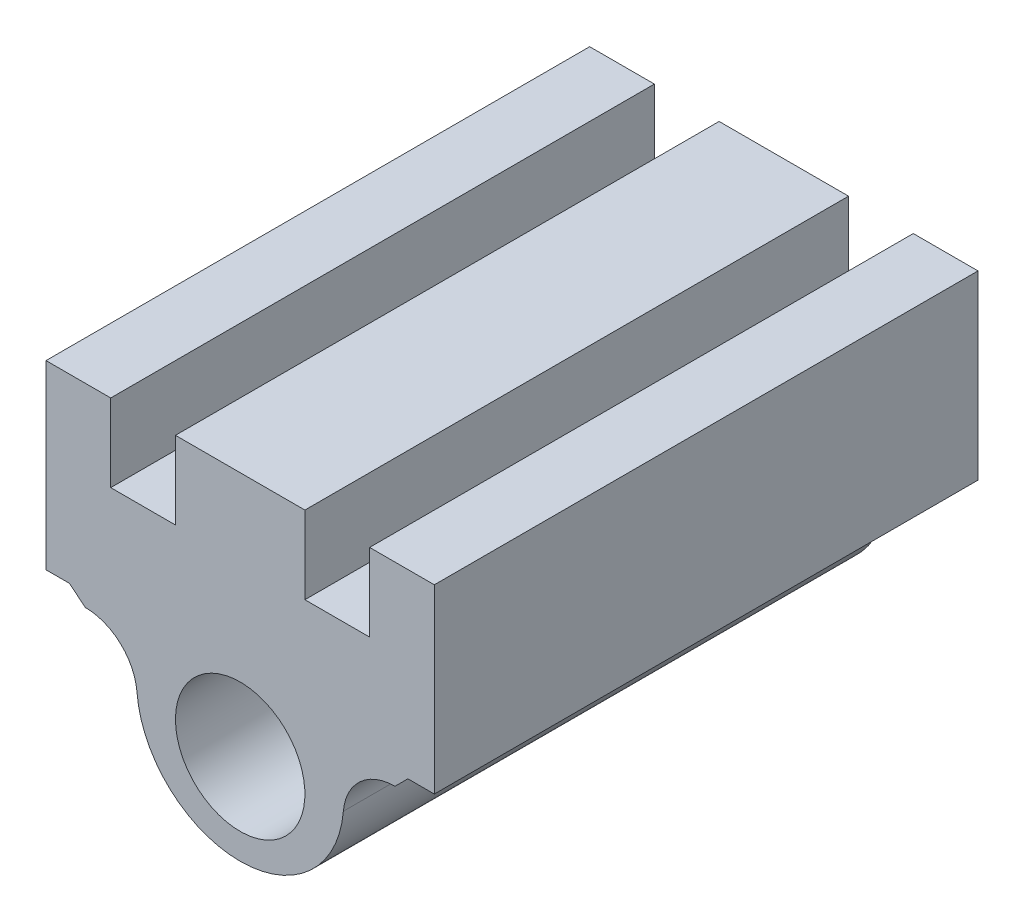
SolidWorks part; units mm, degrees
ref_plane "Front Plane" through (0, 0, 0) normal (0, 0, 1) x (1, 0, 0)
ref_plane "Top Plane" through (0, 0, 0) normal (0, 1, 0) x (1, 0, 0)
ref_plane "Right Plane" through (0, 0, 0) normal (1, 0, 0) x (0, 0, -1)
sketch "Sketch1" plane through (0, 0, 0) normal (0, 1, 0) x (1, 0, 0)
  line L1 (0, 0) -> (60, 0)
  line L2 (0, 0) -> (0, 42)
  line L3 (0, 42) -> (60, 42)
  line L4 (60, 0) -> (60, 42)
  dimension "D1" = 42
  dimension "D2" = 60
extrude "Boss-Extrude1" add sketch "Sketch1" along normal blind 8
sketch "Sketch3" plane through (0, 8, 0) normal (0, 1, 0) x (1, 0, 0)
  line L0 (60, 42) -> (0, 42) construction
  line L1 (25, 42) -> (35, 42)
  line L2 (25, 42) -> (25, 0)
  line L3 (25, 0) -> (35, 0)
  line L4 (35, 42) -> (35, 0)
  line L5 (0, 0) -> (60, 0) construction
  line L6 (0, 42) -> (0, 0) construction
  dimension "D1" = 10
  dimension "D2" = 25
extrude "Boss-Extrude5" add sketch "Sketch3" along normal blind 6
sketch "Sketch5" plane through (0, 0, 0) normal (0, -1, 0) x (1, 0, 0)
  line L0 (0, 0) -> (60, 0) construction
  line L1 (23, 0) -> (37, 0)
  line L2 (23, 0) -> (23, -42)
  line L3 (23, -42) -> (37, -42)
  line L4 (37, 0) -> (37, -42)
  line L5 (60, -42) -> (0, -42) construction
  line L6 (0, -42) -> (0, 0) construction
  dimension "D1" = 14
  dimension "D2" = 23
extrude "Boss-Extrude6" add sketch "Sketch5" along normal blind 11
sketch "Sketch6" plane through (0, 0, -42) normal (0, 0, -1) x (-1, 0, 0)
  line L0 (-23, -11) -> (-23, 0) construction
  line L1 (-37, -11) -> (-37, 0) construction
  line L2 (-23, -11) -> (-37, -11) construction
  circle A0 centre (-30, -5) radius 5
  dimension "D1" = 7
  dimension "D2" = 14
  dimension "D3" = 6
extrude "Cut-Extrude1" cut sketch "Sketch6" against normal through all
fillet "Fillet1" radius 7 2 edges at (23, -11, -21) (37, -11, -21)
fillet "Fillet2" radius 5 1 edges at (23, 0, -21)
fillet "Fillet3" radius 5 1 edges at (37, 0, -21)
sketch "Sketch8" plane through (0, 0, -42) normal (0, 0, -1) x (-1, 0, 0)
  line L0 (-41.9583, -1) -> (-42.9583, 0)
  line L1 (-60, 0) -> (-41.9583, 0) construction
  line L2 (-42.9583, 0) -> (-41.9583, 0)
  line L3 (-18.0417, -1) -> (-16.803, 0)
  line L4 (-18.0417, 0) -> (0, 0) construction
  line L5 (-16.803, 0) -> (-18.0417, 0)
  arc A0 (-18.0417, 0) -> (-23.0243, -4.5833) centre (-18.0417, -5) ccw construction
  arc A1 (-30, -11) -> (-23.0243, -4.5833) centre (-30, -4) ccw construction
  arc A2 (-36.9757, -4.5833) -> (-30, -11) centre (-30, -4) ccw construction
  arc A3 (-36.9757, -4.5833) -> (-41.9583, 0) centre (-41.9583, -5) ccw construction
  arc A4 (-18.0417, 0) -> (-23.0243, -4.5833) centre (-18.0417, -5) ccw
  arc A5 (-30, -11) -> (-23.0243, -4.5833) centre (-30, -4) ccw
  arc A6 (-36.9757, -4.5833) -> (-30, -11) centre (-30, -4) ccw
  arc A7 (-36.9757, -4.5833) -> (-41.9583, 0) centre (-41.9583, -5) ccw
  arc A8 (-18.0417, -1) -> (-22.0278, -4.6667) centre (-18.0417, -5) ccw
  arc A9 (-30, -12) -> (-22.0278, -4.6667) centre (-30, -4) ccw
  arc A10 (-37.9722, -4.6667) -> (-30, -12) centre (-30, -4) ccw
  arc A11 (-37.9722, -4.6667) -> (-41.9583, -1) centre (-41.9583, -5) ccw
  dimension "D1" = 1
extrude "Boss-Extrude7" add sketch "Sketch8" against normal up to surface (42 mm away) up to face at (25, -5, 0)
sketch "Sketch9" plane through (0, 8, 0) normal (0, 1, 0) x (1, 0, 0)
  line L0 (60, 42) -> (35, 42) construction
  line L1 (40, 42) -> (45, 42)
  line L2 (40, 42) -> (40, 0)
  line L3 (40, 0) -> (45, 0)
  line L4 (45, 42) -> (45, 0)
  line L5 (35, 0) -> (60, 0) construction
  line L6 (35, 0) -> (35, 42) construction
  line L7 (25, 42) -> (0, 42) construction
  line L8 (15, 42) -> (20, 42)
  line L9 (15, 42) -> (15, 0)
  line L10 (15, 0) -> (20, 0)
  line L11 (20, 42) -> (20, 0)
  line L12 (0, 0) -> (25, 0) construction
  line L13 (25, 42) -> (25, 0) construction
  dimension "D1" = 5
  dimension "D2" = 5
  dimension "D3" = 5
  dimension "D4" = 5
extrude "Boss-Extrude8" add sketch "Sketch9" along normal blind 6
sketch "Sketch11" plane through (0, 8, 0) normal (0, 1, 0) x (1, 0, 0)
  line L1 (45, 42) -> (60, 42)
  line L2 (45, 42) -> (45, 0)
  line L3 (45, 0) -> (60, 0)
  line L4 (60, 42) -> (60, 0)
  line L5 (0, 42) -> (15, 42)
  line L6 (0, 42) -> (0, 0)
  line L7 (0, 0) -> (15, 0)
  line L8 (15, 42) -> (15, 0)
extrude "Cut-Extrude2" cut sketch "Sketch11" against normal through all
